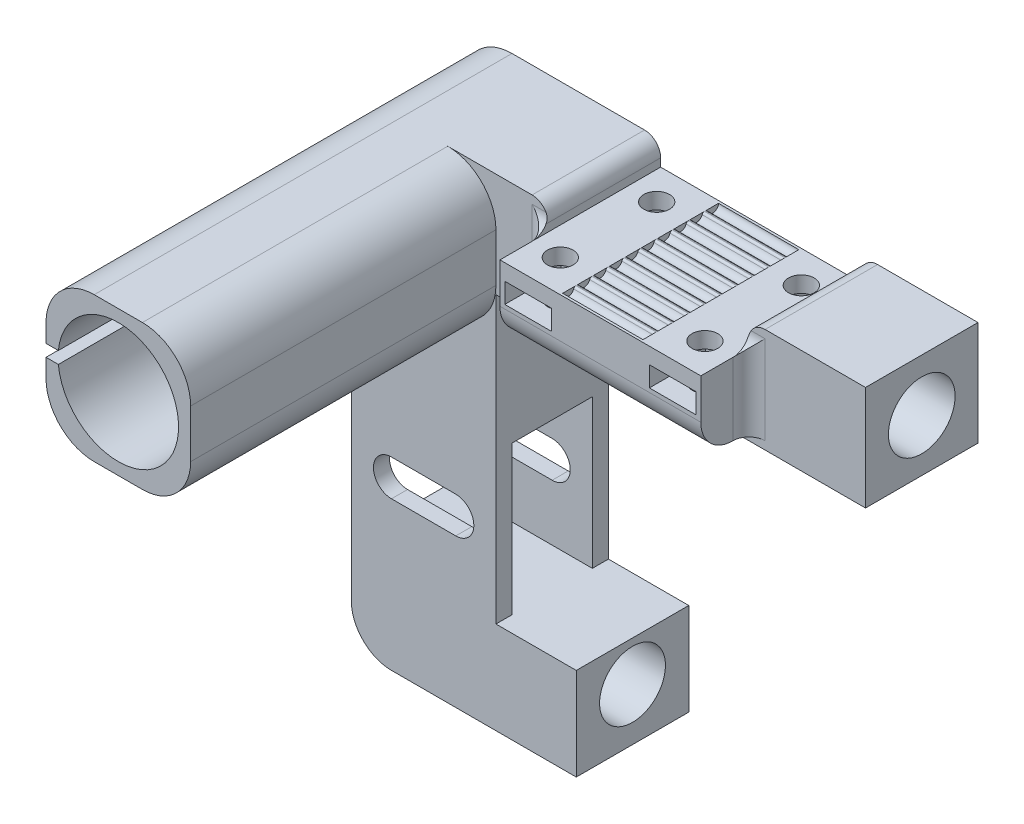
SolidWorks part; units mm, degrees
material "ABS"
ref_plane "Plano frontal" through (0, 0, 0) normal (0, 0, 1) x (1, 0, 0)
ref_plane "Plano superior" through (0, 0, 0) normal (0, 1, 0) x (1, 0, 0)
ref_plane "Plano direito" through (0, 0, 0) normal (1, 0, 0) x (0, 0, -1)
sketch "Esboço1" plane through (0, 0, 0) normal (0, 0, 1) x (1, 0, 0)
  line L0 (0, 30) -> (0, -30) construction
  line L1 (-9, 30) -> (9, 30)
  line L2 (-9, 30) -> (-9, -30)
  line L3 (-9, -30) -> (9, -30)
  line L4 (9, 30) -> (9, -30)
  line L5 (-9, 30) -> (9, -30) construction
  line L6 (-9, -30) -> (9, 30) construction
  line L7 (0, 21) -> (-9, 21) construction
  line L9 (-0.75, 30) -> (0.75, 30)
  line L12 (9, 21.75) -> (9, 20.25)
  line L14 (-9, 21.75) -> (-7.4624, 21.75)
  line L15 (-9, 21.75) -> (-9, 20.25)
  line L16 (-9, 20.25) -> (-7.4624, 20.25)
  line L17 (-7.4624, 21.75) -> (-7.4624, 20.25)
  circle A0 centre (0, 21) radius 7.5
  point P0 (0, 0)
  point P11 (0, 29.2312)
  dimension "D3" = 15
  dimension "D1" = 60
  dimension "D2" = 18
  dimension "D4" = 9
  dimension "D6" = 1.5
extrude "Ressalto-extrusão2" add sketch "Esboço1" along normal mid plane 52 contours A0 L1 L2 L3 L4 region at (0.0208, -4.1716, 0)
sketch "Esboço2" plane through (-9, 0, 0) normal (-1, 0, 0) x (0, 0, 1)
  line L0 (26, 30) -> (-26, 30) construction
  line L1 (26, -30) -> (-12, -30)
  line L2 (26, -30) -> (26, 12)
  line L3 (26, 12) -> (-12, 12)
  line L4 (-12, -30) -> (-12, 12)
  line L5 (-26, 30) -> (-26, 21.75) construction
  dimension "D1" = 18
  dimension "D2" = 14
extrude "Corte-extrusão1" cut sketch "Esboço2" against normal through all
sketch "Esboço3" plane through (9, 0, 0) normal (-1, 0, 0) x (0, 0, 1)
  line L1 (-26, 30) -> (-12, 30)
  line L2 (-26, 30) -> (-26, 17)
  line L3 (-26, 17) -> (-12, 17)
  line L4 (-12, 30) -> (-12, 17)
  dimension "D1" = 13
extrude "Ressalto-extrusão3" add sketch "Esboço3" against normal blind 46
sketch "Esboço4" plane through (55, 0, 0) normal (1, 0, 0) x (0, 0, -1)
  line L0 (19, 30) -> (19, 17) construction
  line L1 (12, 30) -> (26, 30) construction
  line L2 (26, 17) -> (12, 17) construction
  line L3 (26, 23.5) -> (12, 23.5) construction
  line L4 (26, 30) -> (26, 17) construction
  line L5 (12, 17) -> (12, 30) construction
  line L7 (12, 30) -> (26, 30) construction
  circle A0 centre (19, 23.5) radius 4.15
  dimension "D1" = 8.3
  dimension "D2" = 6.5
extrude "Corte-extrusão2" cut sketch "Esboço4" against normal blind 12
sketch "Esboço7" plane through (9, 0, 0) normal (1, 0, 0) x (0, 0, -1)
  line L0 (26, 17) -> (26, -30) construction
  line L1 (12, -30) -> (26, -30)
  line L2 (12, -30) -> (12, -18.5)
  line L3 (12, -18.5) -> (26, -18.5)
  line L4 (26, -30) -> (26, -18.5)
  circle A0 centre (19, -23.5) radius 4.1
  dimension "D2" = 8.2
  dimension "D1" = 11.5
  dimension "D3" = 6.5
extrude "Ressalto-extrusão4" add sketch "Esboço7" along normal blind 10
sketch "Esboço8" plane through (9, 0, 0) normal (1, 0, 0) x (0, 0, -1)
  circle A1 centre (19, -23.5) radius 4.1
  circle A2 centre (19, -23.5) radius 4.1
  dimension "D1" = 0
extrude "Corte-extrusão6" cut sketch "Esboço8" against normal blind 10
sketch "Esboço9" plane through (9, 0, 0) normal (1, 0, 0) x (0, 0, -1)
  line L0 (19, -18.5) -> (19, 17) construction
  line L1 (26, -18.5) -> (12, -18.5) construction
  line L2 (26, 17) -> (12, 17) construction
  line L3 (24, 0) -> (24, -18.5)
  line L4 (24, 0) -> (14, 0)
  line L5 (24, -18.5) -> (14, -18.5)
  line L6 (14, 0) -> (14, -18.5)
  line L7 (24, 0) -> (14, -18.5) construction
  line L8 (24, -18.5) -> (14, 0) construction
  point P7 (19, -9.25)
  dimension "D1" = 18.5
  dimension "D2" = 10
extrude "Corte-extrusão7" cut sketch "Esboço9" against normal through all
sketch "Esboço10" plane through (0, 0, -12) normal (0, 0, 1) x (1, 0, 0)
  line L0 (55, 30) -> (9, 30) construction
  line L1 (15.5, 30) -> (40.5, 30)
  line L2 (15.5, 30) -> (15.5, 18)
  line L3 (15.5, 18) -> (40.5, 18)
  line L4 (40.5, 30) -> (40.5, 18)
  line L5 (9, 17) -> (9, 30) construction
  dimension "D1" = 6.5
  dimension "D2" = 25
  dimension "D3" = 12
extrude "Ressalto-extrusão5" add sketch "Esboço10" along normal blind 6
sketch "Esboço11" plane through (0, 0, -6) normal (0, 0, 1) x (1, 0, 0)
  line L0 (40.5, 18) -> (40.5, 30) construction
  line L1 (15.5, 30) -> (40.5, 30)
  line L2 (15.5, 30) -> (15.5, 27)
  line L3 (15.5, 27) -> (40.5, 27)
  line L4 (40.5, 30) -> (40.5, 27)
  dimension "D1" = 3
extrude "Corte-extrusão8" cut sketch "Esboço11" against normal through all
sketch "Esboço12" plane through (0, 0, -12) normal (0, 0, 1) x (1, 0, 0)
  line L0 (15.5, 18) -> (40.5, 18) construction
  line L1 (23, 18) -> (33, 18)
  line L2 (23, 18) -> (23, 17)
  line L3 (23, 17) -> (33, 17)
  line L4 (33, 18) -> (33, 17)
  line L5 (55, 17) -> (9, 17) construction
  point P8 (28, 18)
  point P9 (28, 18)
  dimension "D1" = 10
extrude "Corte-extrusão9" cut sketch "Esboço12" against normal through all
fillet "Filete1" radius 4 2 edges at (28, 18, -26) (28, 18, -6)
fillet "Filete2" radius 6 4 edges at (-9, 12, 7) (-9, 30, 0) (9, 30, 7) (9, 12, 7)
fillet "Filete3" radius 2 4 edges at (15.5, 22.5, -12) (40.5, 22.5, -12) (40.5, 30, -19) (15.5, 30, -19)
fillet "Filete4" radius 2 2 edges at (41.5, 27, -12) (14.5, 27, -12)
sketch "Esboço13" plane through (0, 27, 0) normal (0, 1, 0) x (1, 0, 0)
  line L0 (28, 6) -> (28, 26) construction
  line L1 (15.5, 6) -> (40.5, 6) construction
  line L2 (15.5, 26) -> (40.5, 26) construction
  line L3 (15.5, 16.0097) -> (40.5, 16.0097) construction
  line L4 (40.5, 26) -> (40.5, 10) construction
  line L5 (15.5, 26) -> (15.5, 10) construction
  circle A0 centre (37, 22.0097) radius 1.6
  circle A1 centre (19, 22.0097) radius 1.6
  circle A2 centre (37, 10.0097) radius 1.6
  circle A3 centre (19, 10.0097) radius 1.6
  dimension "D1" = 3.2
  dimension "D2" = 9
  dimension "D3" = 6
extrude "Corte-extrusão10" cut sketch "Esboço13" against normal blind 8
sketch "Esboço14" plane through (0, 0, -26) normal (0, 0, -1) x (-1, 0, 0)
  line L0 (-28, 27) -> (-28, 22) construction
  line L1 (-15.5, 27) -> (-40.5, 27) construction
  line L2 (-33, 22) -> (-23, 22) construction
  line L3 (-39.9, 25) -> (-39.9, 22.5)
  line L4 (-16.1, 25) -> (-21.9, 25)
  line L5 (-16.1, 25) -> (-16.1, 22.5)
  line L6 (-16.1, 22.5) -> (-21.9, 22.5)
  line L7 (-21.9, 25) -> (-21.9, 22.5)
  line L8 (-39.9, 22.5) -> (-34.1, 22.5)
  line L9 (-39.9, 25) -> (-34.1, 25)
  line L10 (-34.1, 25) -> (-34.1, 22.5)
  point P10 (-19, 25)
  dimension "D1" = 2.5
  dimension "D2" = 2
  dimension "D3" = 5.8
  dimension "D4" = 3.5
extrude "Corte-extrusão11" cut sketch "Esboço14" against normal blind 7
ref_plane "Plano1" through (0, 0, -16) normal (0, 0, 1) x (1, 0, 0)
mirror "Espelhar1" about plane through (0, 0, -16) normal (0, 0, 1) of "Corte-extrusão11"
ref_plane "Plano2" through (28, 0, 0) normal (1, 0, 0) x (0, 0, -1)
sketch "Esboço15" plane through (28, 0, 0) normal (1, 0, 0) x (0, 0, -1)
  line L0 (26, 27) -> (10, 27) construction
  line L1 (24.3, 27) -> (25.7, 27)
  arc A0 (25.7, 27) -> (24.3, 27) centre (25, 27) cw
  dimension "D1" = 0.7
  dimension "D2" = 1
extrude "Corte-extrusão12" cut sketch "Esboço15" against normal blind 5 and the other way blind 5
pattern_linear "Padrão linear1" count 10 spacing 2 along (0, 0, 1) of "Corte-extrusão12"
fillet "Filete5" radius 0.3 18 edges at (28, 27, -24.3) (28, 27, -23.7) (28, 27, -22.3) (28, 27, -21.7) (28, 27, -20.3) (28, 27, -19.7) (28, 27, -18.3) (28, 27, -17.7) (28, 27, -16.3) (28, 27, -15.7) (28, 27, -14.3) (28, 27, -13.7) (28, 27, -12.3) (28, 27, -11.7) (28, 27, -10.3) (28, 27, -9.7) (28, 27, -8.3) (28, 27, -7.7)
sketch "Esboço20" plane through (0, 0, -24) normal (0, 0, 1) x (1, 0, 0)
  line L0 (0, 0) -> (0, -18.5) construction
  line L1 (-9, 0) -> (9, 0) construction
  line L2 (-9, -18.5) -> (9, -18.5) construction
  line L3 (-9, -9.25) -> (9, -9.25) construction
  line L4 (-9, -18.5) -> (-9, 0) construction
  line L5 (9, -18.5) -> (9, 0) construction
  line L6 (-4, -9.25) -> (4, -9.25) construction
  line L7 (-4, -7) -> (4, -7)
  line L8 (-4, -11.5) -> (4, -11.5)
  arc A0 (-4, -7) -> (-4, -11.5) centre (-4, -9.25) ccw
  arc A1 (4, -11.5) -> (4, -7) centre (4, -9.25) ccw
  point P14 (0, -9.25)
  dimension "D1" = 4.5
  dimension "D2" = 8
extrude "Corte-extrusão15" cut sketch "Esboço20" against normal through all and the other way through all
fillet "Filete7" radius 5 1 edges at (-9, -30, -19)
